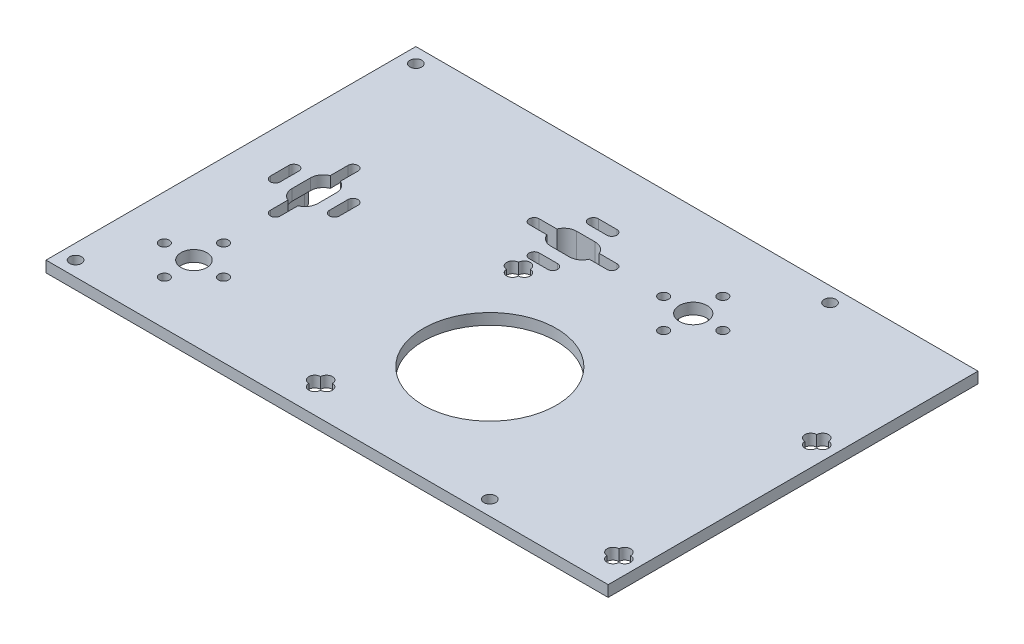
SolidWorks part; units mm, degrees
ref_plane "前视基准面" through (0, 0, 0) normal (0, 0, 1) x (1, 0, 0)
ref_plane "上视基准面" through (0, 0, 0) normal (0, 1, 0) x (1, 0, 0)
ref_plane "右视基准面" through (0, 0, 0) normal (1, 0, 0) x (0, 0, -1)
sketch "Sketch1" plane through (0, 0, 0) normal (0, 1, 0) x (1, 0, 0)
  line L1 (-60, 50) -> (60, 50)
  line L2 (-60, 50) -> (-60, -50)
  line L3 (-60, -50) -> (60, -50)
  line L4 (60, 50) -> (60, -50)
  line L5 (0, -50) -> (0, 50) construction
  line L6 (-60, 0) -> (60, 0) construction
  point P0 (0, 0)
  dimension "D1" = 120
  dimension "D2" = 100
extrude "Boss-Extrude1" add sketch "Sketch1" along normal blind 3
sketch "Sketch2" plane through (0, 3, 0) normal (0, 1, 0) x (1, 0, 0)
  line L0 (60, -50) -> (60, 50) construction
  line L1 (60, 50) -> (-60, 50) construction
  line L2 (-60, -50) -> (60, -50) construction
  line L3 (-60, 50) -> (-60, -50) construction
  line L4 (10, 25) -> (18, 25) construction
  line L5 (-40, 0) -> (-40, -8) construction
  line L6 (40, 25) -> (48, 25) construction
  line L8 (-40, -30) -> (-40, -38) construction
  circle A0 centre (40, 25) radius 14 construction
  circle A1 centre (10, 25) radius 14 construction
  circle A2 centre (-40, 0) radius 14 construction
  circle A3 centre (-40, -30) radius 14 construction
  circle A5 centre (18, 25) radius 1.35
  circle A6 centre (48, 25) radius 1.35
  circle A7 centre (-40, -8) radius 1.35
  circle A8 centre (-40, -38) radius 1.35
  circle A9 centre (10, 17) radius 1.35
  circle A10 centre (2, 25) radius 1.35
  circle A11 centre (10, 33) radius 1.35
  circle A12 centre (40, 17) radius 1.35
  circle A13 centre (32, 25) radius 1.35
  circle A14 centre (40, 33) radius 1.35
  circle A15 centre (-48, -30) radius 1.35
  circle A16 centre (-40, -22) radius 1.35
  circle A17 centre (-32, -30) radius 1.35
  circle A19 centre (-48, 0) radius 1.35
  circle A21 centre (-40, 8) radius 1.35
  circle A23 centre (-32, 0) radius 1.35
  circle A24 centre (-2, 0) radius 1.35 [skipped]
  circle A25 centre (-78, 0) radius 1.35 [skipped]
  circle A26 centre (-40, 38) radius 1.35 [skipped]
  point P33 (10, 25)
  point P40 (40, 25)
  point P47 (-40, -30)
  point P60 (-40, 0)
  dimension "D1" = 28
  dimension "D8" = 2.7
  dimension "D11" = 2.7
  dimension "D2" = 20
  dimension "D3" = 25
  dimension "D4" = 20
  dimension "D5" = 20
  dimension "D6" = 30
  dimension "D7" = 30
  dimension "D9" = 8
  dimension "D10" = 8
  dimension "D12" = 8
  dimension "D13" = 4
  dimension "D14" = 4
  dimension "D15" = 4
  dimension "D16" = 4
extrude "Cut-Extrude1" cut sketch "Sketch2" against normal blind 4
sketch "Sketch3" plane through (0, 3, 0) normal (0, 1, 0) x (1, 0, 0)
  line L0 (-40, -8) -> (-40, -22) construction
  line L2 (18, 25) -> (32, 25) construction
  line L4 (-40, -15) -> (25, -15) construction
  line L5 (25, -15) -> (25, 25) construction
  circle A0 centre (25, -15) radius 18
  circle A1 centre (25, -3.75) radius 1.6 construction
  circle A2 centre (36.25, -15) radius 1.6 construction
  circle A3 centre (25, -26.25) radius 1.6 construction
  circle A4 centre (13.75, -15) radius 1.6 construction
  point P23 (25, -15)
  dimension "D1" = 36
  dimension "D2" = 11.25
  dimension "D3" = 3.2
  dimension "D4" = 4
extrude "Cut-Extrude2" cut sketch "Sketch3" against normal blind 10
sketch "Sketch4" plane through (0, 3, 0) normal (0, 1, 0) x (1, 0, 0)
  line L0 (-40, -8) -> (-40, -3) construction
  line L1 (-41.35, -8) -> (-41.35, -3)
  line L2 (-38.65, -8) -> (-38.65, -3)
  line L3 (-32, 0) -> (-32, 5) construction
  line L4 (-33.35, 0) -> (-33.35, 5)
  line L5 (-30.65, 0) -> (-30.65, 5)
  line L6 (-40, 8) -> (-40, 13) construction
  line L7 (-41.35, 8) -> (-41.35, 13)
  line L8 (-38.65, 8) -> (-38.65, 13)
  line L9 (-48, 0) -> (-48, 5) construction
  line L10 (-49.35, 0) -> (-49.35, 5)
  line L11 (-46.65, 0) -> (-46.65, 5)
  line L12 (2, 25) -> (-3, 25) construction
  line L13 (2, 23.65) -> (-3, 23.65)
  line L14 (2, 26.35) -> (-3, 26.35)
  line L15 (10, 33) -> (5, 33) construction
  line L16 (10, 31.65) -> (5, 31.65)
  line L17 (10, 34.35) -> (5, 34.35)
  line L18 (18, 25) -> (13, 25) construction
  line L19 (18, 23.65) -> (13, 23.65)
  line L20 (18, 26.35) -> (13, 26.35)
  line L21 (10, 17) -> (5, 17) construction
  line L22 (10, 15.65) -> (5, 15.65)
  line L23 (10, 18.35) -> (5, 18.35)
  arc A0 (-41.35, -8) -> (-38.65, -8) centre (-40, -8) ccw
  arc A1 (-38.65, -3) -> (-41.35, -3) centre (-40, -3) ccw
  arc A2 (-33.35, 0) -> (-30.65, 0) centre (-32, 0) ccw
  arc A3 (-30.65, 5) -> (-33.35, 5) centre (-32, 5) ccw
  arc A4 (-41.35, 8) -> (-38.65, 8) centre (-40, 8) ccw
  arc A5 (-38.65, 13) -> (-41.35, 13) centre (-40, 13) ccw
  arc A6 (-49.35, 0) -> (-46.65, 0) centre (-48, 0) ccw
  arc A7 (-46.65, 5) -> (-49.35, 5) centre (-48, 5) ccw
  arc A8 (2, 23.65) -> (2, 26.35) centre (2, 25) ccw
  arc A9 (-3, 26.35) -> (-3, 23.65) centre (-3, 25) ccw
  arc A10 (10, 31.65) -> (10, 34.35) centre (10, 33) ccw
  arc A11 (5, 34.35) -> (5, 31.65) centre (5, 33) ccw
  arc A12 (18, 23.65) -> (18, 26.35) centre (18, 25) ccw
  arc A13 (13, 26.35) -> (13, 23.65) centre (13, 25) ccw
  arc A14 (10, 15.65) -> (10, 18.35) centre (10, 17) ccw
  arc A15 (5, 18.35) -> (5, 15.65) centre (5, 17) ccw
  circle A16 centre (18, 25) radius 1.35 construction
  point P3 (-40, -5.5)
  point P8 (-32, 2.5)
  point P16 (-40, 10.5)
  point P24 (-48, 2.5)
  point P32 (-0.5, 25)
  point P40 (7.5, 33)
  point P48 (15.5, 25)
  point P56 (7.5, 17)
  dimension "D1" = 5
extrude "Cut-Extrude3" cut sketch "Sketch4" against normal blind 10
sketch "Sketch5" plane through (0, 3, 0) normal (0, 1, 0) x (1, 0, 0)
  line L0 (-60, -50) -> (60, -50) construction
  line L1 (-56, -46) -> (56, -46) construction
  line L2 (-56, -46) -> (-56, 46) construction
  line L3 (-56, 46) -> (56, 46) construction
  line L4 (56, -46) -> (56, 46) construction
  line L5 (0, 46) -> (0, -46) construction
  line L6 (-56, 0) -> (56, 0) construction
  line L7 (-60, 50) -> (-60, -50) construction
  circle A0 centre (-56, 46) radius 1.6
  circle A1 centre (56, 46) radius 1.6
  circle A2 centre (56, -46) radius 1.6
  circle A3 centre (-56, -46) radius 1.6
  point P0 (0, 0)
  dimension "D1" = 3.2
  dimension "D2" = 4
  dimension "D3" = 4
extrude "Cut-Extrude5" cut sketch "Sketch5" against normal blind 10
sketch "Sketch6" plane through (0, 3, 0) normal (0, 1, 0) x (1, 0, 0)
  line L0 (40, 17) -> (40, 33) construction
  line L1 (-40, 0) -> (-40, 5) construction
  line L2 (-40, -22) -> (-40, -38) construction
  line L3 (-43.5, 0) -> (-43.5, 5)
  line L4 (-40, -8) -> (-40, 8) construction
  line L5 (-36.5, 0) -> (-36.5, 5)
  line L6 (2, 25) -> (18, 25) construction
  line L9 (10, 25) -> (5, 25) construction
  line L10 (10, 21.5) -> (5, 21.5)
  line L11 (10, 28.5) -> (5, 28.5)
  arc A0 (-43.5, 0) -> (-36.5, 0) centre (-40, 0) ccw
  arc A1 (-36.5, 5) -> (-43.5, 5) centre (-40, 5) ccw
  circle A3 centre (-40, -30) radius 3.5
  arc A4 (10, 21.5) -> (10, 28.5) centre (10, 25) ccw
  arc A5 (5, 28.5) -> (5, 21.5) centre (5, 25) ccw
  circle A6 centre (40, 25) radius 3.75
  point P18 (-40, 2.5)
  point P27 (7.5, 25)
  dimension "D1" = 3.5
  dimension "D3" = 7
  dimension "D4" = 7.5
  dimension "D6" = 3.5
  dimension "D2" = 5
  dimension "D5" = 5
extrude "Cut-Extrude6" cut sketch "Sketch6" against normal blind 10
sketch "Sketch9" plane through (60, 0, 0) normal (1, 0, 0) x (0, 0, -1)
  line L4 (-50, 0) -> (50, 0)
  line L5 (50, 0) -> (50, 3)
  line L6 (50, 3) -> (-50, 3)
  line L7 (-50, 3) -> (-50, 0)
  line L8 (-50, 0) -> (50, 0)
  line L9 (50, 0) -> (50, 3)
  line L10 (50, 3) -> (-50, 3)
  line L11 (-50, 3) -> (-50, 0)
  dimension "D1" = 0
extrude "Boss-Extrude2" add sketch "Sketch9" along normal blind 32
sketch "Sketch8" plane through (0, 0, 0) normal (0, -1, 0) x (1, 0, 0)
  line L1 (86.65, 41.75) -> (6, 41.75) construction
  line L2 (86.65, 41.75) -> (86.65, -11.75) construction
  line L3 (86.65, -11.75) -> (6, -11.75) construction
  line L4 (6, 41.75) -> (6, -11.75) construction
  line L5 (46.325, -11.75) -> (46.325, 41.75) construction
  line L6 (86.65, 15) -> (6, 15) construction
  circle A0 centre (25, 15) radius 9.4474 construction
  circle A1 centre (6, -11.75) radius 1.6
  circle A2 centre (6, 41.75) radius 1.6
  circle A3 centre (86.65, 41.75) radius 1.6
  circle A4 centre (86.65, -11.75) radius 1.6
  point P3 (46.325, 15)
  dimension "D1" = 19
  dimension "D4" = 3.2
  dimension "D2" = 53.5
  dimension "D3" = 80.65
extrude "Cut-Extrude8" cut sketch "Sketch8" against normal blind 10
sketch "Sketch10" plane through (0, 0, 0) normal (0, -1, 0) x (1, 0, 0)
  line L0 (4.4, 41.75) -> (7.6, 41.75) construction
  line L3 (6, 43.35) -> (6, 40.15) construction
  line L6 (6, -13.35) -> (6, -10.15) construction
  line L9 (4.4, -11.75) -> (7.6, -11.75) construction
  line L12 (86.65, -13.35) -> (86.65, -10.15) construction
  line L15 (86.65, 43.35) -> (86.65, 40.15) construction
  line L18 (85.05, 41.75) -> (88.25, 41.75) construction
  line L21 (85.05, -11.75) -> (88.25, -11.75) construction
  arc A0 (4.4, 43.35) -> (4.4, 40.15) centre (4.4, 41.75) ccw
  arc A1 (7.6, 40.15) -> (7.6, 43.35) centre (7.6, 41.75) ccw
  arc A2 (7.6, 43.35) -> (4.4, 43.35) centre (6, 43.35) ccw
  arc A3 (4.4, 40.15) -> (7.6, 40.15) centre (6, 40.15) ccw
  arc A4 (4.4, -13.35) -> (7.6, -13.35) centre (6, -13.35) ccw
  arc A5 (7.6, -10.15) -> (4.4, -10.15) centre (6, -10.15) ccw
  arc A6 (4.4, -10.15) -> (4.4, -13.35) centre (4.4, -11.75) ccw
  arc A7 (7.6, -13.35) -> (7.6, -10.15) centre (7.6, -11.75) ccw
  arc A8 (85.05, -13.35) -> (88.25, -13.35) centre (86.65, -13.35) ccw
  arc A9 (88.25, -10.15) -> (85.05, -10.15) centre (86.65, -10.15) ccw
  arc A10 (88.25, 43.35) -> (85.05, 43.35) centre (86.65, 43.35) ccw
  arc A11 (85.05, 40.15) -> (88.25, 40.15) centre (86.65, 40.15) ccw
  arc A12 (85.05, 43.35) -> (85.05, 40.15) centre (85.05, 41.75) ccw
  arc A13 (88.25, 40.15) -> (88.25, 43.35) centre (88.25, 41.75) ccw
  arc A14 (85.05, -10.15) -> (85.05, -13.35) centre (85.05, -11.75) ccw
  arc A15 (88.25, -13.35) -> (88.25, -10.15) centre (88.25, -11.75) ccw
  circle A16 centre (86.65, -11.75) radius 1.6 construction
  point P2 (6, 41.75)
  point P9 (6, 41.75)
  point P16 (6, -11.75)
  point P24 (6, -11.75)
  point P31 (86.65, -11.75)
  point P39 (86.65, 41.75)
  point P47 (86.65, 41.75)
  point P54 (86.65, -11.75)
extrude "Cut-Extrude9" cut sketch "Sketch10" against normal blind 60
sketch "Sketch11" plane through (0, 0, 0) normal (0, -1, 0) x (1, 0, 0)
  line L8 (-49.35, -5) -> (-49.35, 0) construction
  line L9 (-46.65, 0) -> (-46.65, -5) construction
  line L10 (-33.35, -5) -> (-33.35, 0) construction
  line L11 (-30.65, 0) -> (-30.65, -5) construction
  line L12 (-49.35, -5) -> (-49.35, 0)
  line L13 (-46.65, 0) -> (-46.65, -5)
  line L14 (-33.35, -5) -> (-33.35, 0)
  line L15 (-30.65, 0) -> (-30.65, -5)
  line L17 (-50.85, -5) -> (-50.85, 0)
  line L18 (-45.15, 0) -> (-45.15, -5)
  line L19 (-34.85, -5) -> (-34.85, 0)
  line L20 (-29.15, 0) -> (-29.15, -5)
  line L21 (10, -20) -> (5, -20)
  line L22 (0.8918, -22.15) -> (-3, -22.15)
  line L23 (10, -21.5) -> (5, -21.5)
  line L24 (18, -23.65) -> (13.2292, -23.65)
  line L25 (13.2292, -26.35) -> (18, -26.35)
  line L26 (5, -28.5) -> (10, -28.5)
  line L27 (-3, -26.35) -> (1.7708, -26.35)
  line L28 (1.7708, -23.65) -> (-3, -23.65)
  line L29 (10, -21.5) -> (5, -21.5)
  line L30 (18, -23.65) -> (13.2292, -23.65)
  line L31 (13.2292, -26.35) -> (18, -26.35)
  line L32 (5, -28.5) -> (10, -28.5)
  line L33 (-3, -26.35) -> (1.7708, -26.35)
  line L34 (1.7708, -23.65) -> (-3, -23.65)
  line L35 (-3, -27.85) -> (0.8918, -27.85)
  line L36 (5, -30) -> (10, -30)
  line L37 (14.1082, -27.85) -> (18, -27.85)
  line L38 (18, -22.15) -> (14.1082, -22.15)
  circle A4 centre (-40, 22) radius 1.35 construction
  circle A5 centre (-40, 38) radius 1.35 construction
  circle A6 centre (-32, 30) radius 1.35 construction
  circle A7 centre (-48, 30) radius 1.35 construction
  circle A8 centre (-40, 22) radius 1.35
  circle A9 centre (-40, 38) radius 1.35
  circle A10 centre (-32, 30) radius 1.35
  circle A11 centre (-48, 30) radius 1.35
  circle A16 centre (48, -25) radius 1.35 construction
  circle A17 centre (40, -17) radius 1.35 construction
  circle A18 centre (32, -25) radius 1.35 construction
  circle A19 centre (40, -33) radius 1.35 construction
  circle A24 centre (48, -25) radius 1.35
  circle A25 centre (40, -17) radius 1.35
  circle A26 centre (32, -25) radius 1.35
  circle A27 centre (40, -33) radius 1.35
  arc A28 (-49.35, -5) -> (-46.65, -5) centre (-48, -5) ccw construction
  arc A29 (-46.65, 0) -> (-49.35, 0) centre (-48, 0) ccw construction
  arc A30 (-33.35, -5) -> (-30.65, -5) centre (-32, -5) ccw construction
  arc A31 (-30.65, 0) -> (-33.35, 0) centre (-32, 0) ccw construction
  arc A32 (-49.35, -5) -> (-46.65, -5) centre (-48, -5) ccw
  arc A33 (-46.65, 0) -> (-49.35, 0) centre (-48, 0) ccw
  arc A34 (-33.35, -5) -> (-30.65, -5) centre (-32, -5) ccw
  arc A35 (-30.65, 0) -> (-33.35, 0) centre (-32, 0) ccw
  arc A36 (-45.15, 0) -> (-50.85, 0) centre (-48, 0) ccw
  arc A37 (-50.85, -5) -> (-45.15, -5) centre (-48, -5) ccw
  arc A38 (-29.15, 0) -> (-34.85, 0) centre (-32, 0) ccw
  arc A39 (-34.85, -5) -> (-29.15, -5) centre (-32, -5) ccw
  arc A40 (5, -20) -> (0.8918, -22.15) centre (5, -25) ccw
  arc A41 (-3, -22.15) -> (-3, -27.85) centre (-3, -25) ccw
  arc A42 (13.2292, -23.65) -> (10, -21.5) centre (10, -25) ccw
  arc A43 (18, -26.35) -> (18, -23.65) centre (18, -25) ccw
  arc A44 (10, -28.5) -> (13.2292, -26.35) centre (10, -25) ccw
  arc A45 (1.7708, -26.35) -> (5, -28.5) centre (5, -25) ccw
  arc A46 (-3, -23.65) -> (-3, -26.35) centre (-3, -25) ccw
  arc A47 (5, -21.5) -> (1.7708, -23.65) centre (5, -25) ccw
  arc A48 (13.2292, -23.65) -> (10, -21.5) centre (10, -25) ccw
  arc A49 (18, -26.35) -> (18, -23.65) centre (18, -25) ccw
  arc A50 (10, -28.5) -> (13.2292, -26.35) centre (10, -25) ccw
  arc A51 (1.7708, -26.35) -> (5, -28.5) centre (5, -25) ccw
  arc A52 (-3, -23.65) -> (-3, -26.35) centre (-3, -25) ccw
  arc A53 (5, -21.5) -> (1.7708, -23.65) centre (5, -25) ccw
  arc A54 (0.8918, -27.85) -> (5, -30) centre (5, -25) ccw
  arc A55 (10, -30) -> (14.1082, -27.85) centre (10, -25) ccw
  arc A56 (18, -27.85) -> (18, -22.15) centre (18, -25) ccw
  arc A57 (14.1082, -22.15) -> (10, -20) centre (10, -25) ccw
  circle A58 centre (-40, 22) radius 2.85
  circle A59 centre (-40, 38) radius 2.85
  circle A60 centre (-32, 30) radius 2.85
  circle A61 centre (-48, 30) radius 2.85
  circle A62 centre (48, -25) radius 2.85
  circle A63 centre (40, -17) radius 2.85
  circle A64 centre (32, -25) radius 2.85
  circle A65 centre (40, -33) radius 2.85
  dimension "D1" = 0
  dimension "D2" = 1.5
extrude "Boss-Extrude3" add sketch "Sketch11" along normal blind 5
equation "\"D4@Sketch2\"=\"D5@Sketch2\""
equation "\"D2@Sketch2\"=\"D5@Sketch2\""
equation "\"D3@Sketch5\"=\"D2@Sketch5\""
